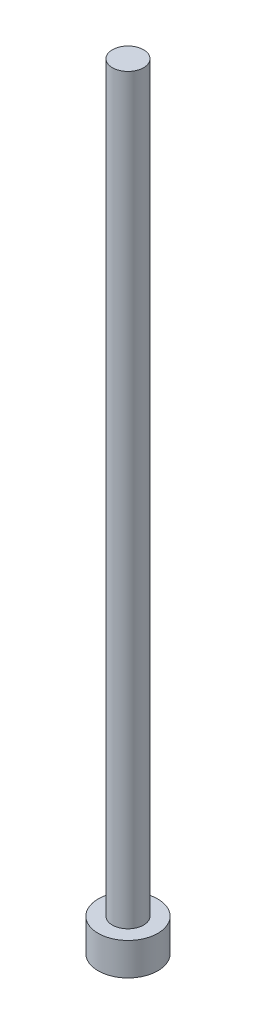
SolidWorks part; units mm, degrees
ref_plane "前视基准面" through (0, 0, 0) normal (0, 0, 1) x (1, 0, 0)
ref_plane "上视基准面" through (0, 0, 0) normal (0, 1, 0) x (1, 0, 0)
ref_plane "右视基准面" through (0, 0, 0) normal (1, 0, 0) x (0, 0, -1)
other "Configuration Table"
sketch "草图1" plane through (0, 0, 0) normal (0, 1, 0) x (1, 0, 0)
  line L1 (1.1547, 0) -> (0.5774, 1)
  line L2 (0.5774, 1) -> (-0.5774, 1)
  line L3 (-0.5774, 1) -> (-1.1547, 0)
  line L4 (-1.1547, 0) -> (-0.5774, -1)
  line L5 (-0.5774, -1) -> (0.5774, -1)
  line L6 (0.5774, -1) -> (1.1547, 0)
  circle A0 centre (0, 0) radius 1 construction
  circle A1 centre (0, 0) radius 2.2
  circle A2 centre (0, 0) radius 1.15
  dimension "D1" = 2
  dimension "D2" = 4.4
  dimension "D3" = 2.3
extrude "凸台-拉伸1" add sketch "草图1" along normal blind 2.4 contours A1
extrude "凸台-拉伸2" add sketch "草图1<4>" along normal blind 54.8 from surface contours A2 starting at face at (0, 2.4, 2.2)
sketch "草图1<4>" plane through (0, 0, 0) normal (0, 1, 0) x (1, 0, 0) same geometry as "草图1"
extrude "切除-拉伸1" cut sketch "草图1<3>" along normal blind 1.5 contours L5 A2 L6 L1 L2 L3 L4 region at (0, 0, 0)
sketch "草图1<3>" plane through (0, 0, 0) normal (0, 1, 0) x (1, 0, 0) same geometry as "草图1"
